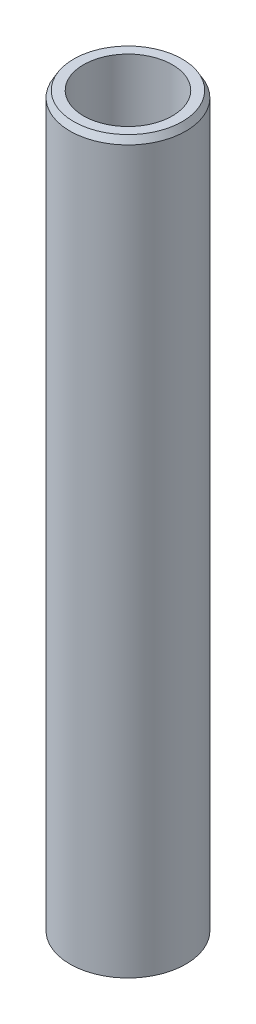
SolidWorks part; units mm, degrees
ref_plane "Front Plane" through (0, 0, 0) normal (0, 0, 1) x (1, 0, 0)
ref_plane "Top Plane" through (0, 0, 0) normal (0, 1, 0) x (1, 0, 0)
ref_plane "Right Plane" through (0, 0, 0) normal (1, 0, 0) x (0, 0, -1)
sketch "Sketch1" plane through (0, 0, 0) normal (0, 1, 0) x (1, 0, 0)
  circle A0 centre (0, 0) radius 45
  dimension "SHAFT_OD" = 90
extrude "Boss-Extrude1" add sketch "Sketch1" along normal blind 568.0669
sketch "Sketch2" plane through (0, 0, 0) normal (0, 1, 0) x (1, 0, 0)
  circle A0 centre (0, 0) radius 34.4983
  dimension "BORE_D" = 68.9966
extrude "Cut-Extrude1" cut sketch "Sketch2" along normal through all
chamfer "Chamfer1" distance 4.9492 angle 30 2 edges at (0, 568.0669, 45) (0, 0, 45) first distance on face at (0, 568.0669, 45) first distance on face at (0, 0, 34.4983)
